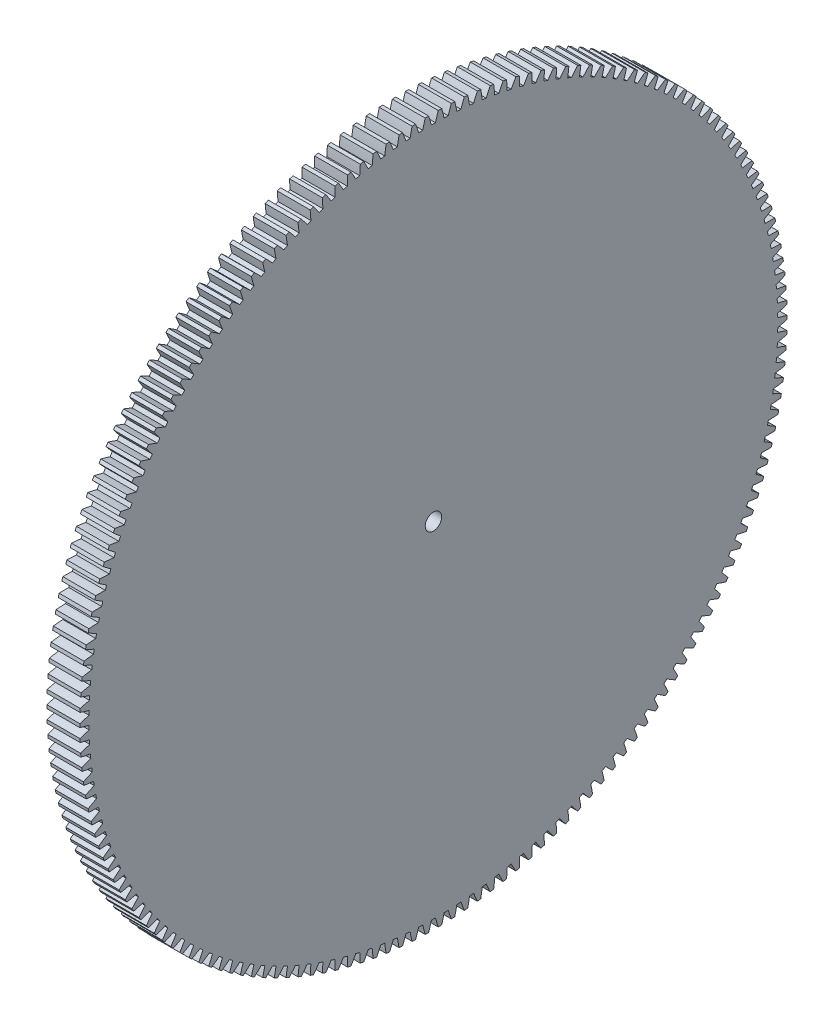
SolidWorks part; units mm, degrees
ref_plane "Plane1" through (0, 0, 0) normal (0, 0, 1) x (1, 0, 0)
ref_plane "Plane2" through (0, 0, 0) normal (0, 1, 0) x (1, 0, 0)
ref_plane "Plane3" through (0, 0, 0) normal (1, 0, 0) x (0, 0, -1)
other "Configuration Table"
sketch "HoldingSke" plane through (0, 0, 0) normal (0, 1, 0) x (1, 0, 0)
  line L0 (0, 0) -> (-1.9696, -0.3473)
  line L1 (-15, 0) -> (100, 0) construction
  line L2 (0, 0) -> (-2.1039, 2.3779)
  line L3 (0, 0) -> (-11.863, 4.5341)
  line L4 (0, 0) -> (-8.5048, 1.4996)
  line L5 (0, 0) -> (-46.8476, -17.4728)
  line L6 (0, 0) -> (-3.3159, -2.2372)
  line L7 (-2.1039, 2.3779) -> (8.6586, 51.2059)
  line L8 (-76.2, 54.61) -> (-75.9, 54.61)
  line L9 (-67.7845, 28.3722) -> (-49.3413, 33.142)
  line L10 (-76.2, 71.12) -> (104.1128, 71.12)
  line L11 (0, 0) -> (-4, 0)
  line L12 (-76.2, 101.6) -> (-76.181, 101.6)
  line L13 (24.9733, 27.94) -> (52.9518, 28.4284)
  line L14 (24.9733, 27.94) -> (24.9743, 27.94)
  line L15 (24.9733, 27.94) -> (100.4006, 29.5858)
  line L16 (-63.627, -0.5) -> (-12.827, -0.5)
  circle A0 centre (0, 0) radius 1
  circle A1 centre (0, 0) radius 37.5
  circle A2 centre (0, 0) radius 37.5
  circle A3 centre (0, 0) radius 1
  dimension "Pitch_radius" = 180.3128
  dimension "Width" = 4
  dimension "Thickness" = 4
sketch "BasProSke" plane through (0, 0, 0) normal (0, 1, 0) x (1, 0, 0)
  line L0 (-10, 0) -> (60, 0) construction
  line L1 (0, 0) -> (0, 43)
  line L2 (0, 0) -> (4, 0)
  line L3 (4, 0) -> (4, 43)
  line L4 (4, 43) -> (0, 43)
  dimension "Thickness" = 4
revolve "Base-Revolve" add sketch "BasProSke" angle 360 about L0
sketch "TooCutSke" plane through (0, 0, 0) normal (1, 0, 0) x (0, 0, -1)
  line L1 (0, 0) -> (0, 107) construction
  line L2 (0, 0) -> (-0.4259, 42.4979) construction
  line L3 (0, 0) -> (-1.5707, 84.9824) construction
  line L4 (-0.4259, 42.4979) -> (-0.7853, 42.4912) construction
  arc A0 (0.251, 41.8732) -> (-0.251, 41.8732) centre (0, 0) ccw
  arc A1 (0.5926, 43.0213) -> (-0.5926, 43.0213) centre (0, 0) ccw
  circle A2 centre (0, 0) radius 42.5 construction
  circle A3 centre (0, 0) radius 41.1463 construction
  arc A4 (-0.251, 41.8732) -> (-0.5926, 43.0213) centre (-16.7058, 37.6023) ccw
  arc A5 (0.5926, 43.0213) -> (0.251, 41.8732) centre (16.7058, 37.6023) ccw
extrude "ToothCut" cut sketch "TooCutSke" along normal through all
fillet "Breaks" [suppressed] radius 0.01 tangent propagation no
fillet "RootFillets" [suppressed] radius 0.126
pattern_circular "TeethCuts" count 170 every 2.118 about axis through (-10, 0, 0) along (1, 0, 0) of "ToothCut", "RootFillets", "Breaks"
sketch "HubNeaOneSke" plane through (0, 0, 0) normal (-1, 0, 0) x (0, 0, 1)
  circle A0 centre (0, 0) radius 37.5
  dimension "Diameter" = 75
extrude "HubNearOne" [suppressed] add sketch "HubNeaOneSke" along normal blind 46.0001
sketch "HubNeaBotSke" plane through (0, 0, 0) normal (-1, 0, 0) x (0, 0, 1)
  circle A0 centre (0, 0) radius 37.5
  dimension "Diameter" = 75
extrude "HubNearBoth" [suppressed] add sketch "HubNeaBotSke" along normal blind 23
ref_plane "FarPln" through (4, 0, 0) normal (1, 0, 0) x (0, 0, -1)
sketch "HubFarSke" plane through (4, 0, 0) normal (1, 0, 0) x (0, 0, -1)
  circle A0 centre (0, 0) radius 37.5
  dimension "Diameter" = 75
extrude "HubFar" [suppressed] add sketch "HubFarSke" along normal blind 23
sketch "BorSke" plane through (0, 0, 0) normal (1, 0, 0) x (0, 0, -1)
  circle A0 centre (0, 0) radius 1
  dimension "Diameter" = 2
extrude "Bore" cut sketch "BorSke" along normal mid plane 100.0001
sketch "KeySke" plane through (0, 0, 0) normal (1, 0, 0) x (0, 0, -1)
  line L0 (-0.4, 0) -> (-0.4, 1.3)
  line L1 (-0.4, 1.3) -> (0.4, 1.3)
  line L2 (0.4, 1.3) -> (0.4, 0)
  line L3 (0, 0) -> (0, 34) construction
  line L4 (-0.4, 0) -> (0.4, 0)
  dimension "Width" = 0.8
extrude "Keyway" [suppressed] cut sketch "KeySke" along normal mid plane 100.0001
pattern_circular "Keyway2" [suppressed] count 2 every 90 about axis through (-10, 0, 0) along (1, 0, 0) reverse direction yes
equation "' \"Module@HoldingSke\" = 6.35"
equation "' \"Num_teeth@HoldingSke\" = 12"
equation "' \"Ap@HoldingSke\" =  20"
equation "' \"Ap@HoldingSke\" = 20"
equation "' \"Width@HoldingSke\" = 0.5 * 25.4"
equation "' \"Hub_dia@HoldingSke\"= 1 * 25.4"
equation "' \"Hub_dia@HoldingSke\" = 1 * 25.4"
equation "' \"Overall_len@HoldingSke\" = 1.0 * 25.4"
equation "' \"Bore@HoldingSke\" = 0.75 * 25.4"
equation "' \"T_dim@HoldingSke\" = 0.1 * 25.4"
equation "' \"Width@KeySke\" = 0.25 * 25.4"
equation "' \"Show_teeth@HoldingSke\" = 13"
equation "' \"Backlash@HoldingSke\" = 0.009 * 25.4"
equation "' \"Addendum_fac@HoldingSke\" = 1.0"
equation "' \"Dedendum_fac@HoldingSke\" = 1.25"
equation "' \"Dedendum_add@HoldingSke\" = 0.00005 * 25.4"
equation "' \"Clearance_fac@HoldingSke\" = 0.25"
equation "\"Pitch@HoldingSke\" = 1 / \"Module@HoldingSke\""
equation "\"Overcut_dia@TooCutSke\" = (\"Num_teeth@HoldingSke\" + 2 * \"Addendum_fac@HoldingSke\") / \"Pitch@HoldingSke\" + 0.002 * 25.4"
equation "\"Pitch_dia@TooCutSke\" = \"Num_teeth@HoldingSke\" / \"Pitch@HoldingSke\""
equation "\"Base_dia@TooCutSke\" = \"Num_teeth@HoldingSke\" / \"Pitch@HoldingSke\" * cos((\"Ap@HoldingSke\"  * 3.14159265 / 180))"
equation "\"Root_dia@TooCutSke\" = (\"Num_teeth@HoldingSke\" + 2) / \"Pitch@HoldingSke\" - 2 * (\"Addendum_fac@HoldingSke\" + \"Dedendum_fac@HoldingSke\") / \"Pitch@HoldingSke\" - \"Dedendum_add@HoldingSke\" * 2"
equation "\"Half_ang@TooCutSke\" = 180 / \"Num_teeth@HoldingSke\""
equation "\"Half_CT@TooCutSke\" = \"Num_teeth@HoldingSke\" / \"Pitch@HoldingSke\" * sin((3.14159265 / 2 / \"Num_teeth@HoldingSke\")) / 2 - 7 * \"Backlash@HoldingSke\" / 4"
equation "\"Flank_rad@TooCutSke\" = \"Num_teeth@HoldingSke\" / \"Pitch@HoldingSke\" / 5"
equation "\"Radius@RootFillets\" = \"Clearance_fac@HoldingSke\" / \"Pitch@HoldingSke\" + \"Dedendum_add@HoldingSke\""
equation "\"Break_rad@Breaks\" = 0.02 / \"Pitch@HoldingSke\""
equation "\"Thickness@HoldingSke\" = \"Width@HoldingSke\""
equation "\"OAL@HoldingSke\" = \"Thickness@HoldingSke\""
equation "\"MHD@HoldingSke\" = (\"Num_teeth@HoldingSke\" + 2) / \"Pitch@HoldingSke\" - 2 * (\"Addendum_fac@HoldingSke\" + \"Dedendum_fac@HoldingSke\")  / \"Pitch@HoldingSke\" - \"Dedendum_add@HoldingSke\" * 2"
equation "\"MBD@HoldingSke\" = (\"Num_teeth@HoldingSke\" + 2) / \"Pitch@HoldingSke\" - 2 * (\"Addendum_fac@HoldingSke\" + \"Dedendum_fac@HoldingSke\")  / \"Pitch@HoldingSke\" - \"Dedendum_add@HoldingSke\" * 2 - 0.002 * 25.4"
equation "\"MHD@HoldingSke\" = ((sgn( \"MHD@HoldingSke\" - \"Hub_dia@HoldingSke\" )-1)*( \"MHD@HoldingSke\" - \"Hub_dia@HoldingSke\" ))/-2+ \"Hub_dia@HoldingSke\""
equation "\"MBD@HoldingSke\" = ((sgn( \"MBD@HoldingSke\" - \"Bore@HoldingSke\" )-1)*( \"MBD@HoldingSke\" - \"Bore@HoldingSke\" ))/-2+ \"Bore@HoldingSke\""
equation "\"OAL@HoldingSke\" = ((sgn( \"OAL@HoldingSke\" - \"Overall_len@HoldingSke\" )+1)*( \"OAL@HoldingSke\" - \"Overall_len@HoldingSke\" ))/2 + \"Overall_len@HoldingSke\" + 0.000002 * 25.4"
equation "\"Num_teeth@TeethCuts\" = int( \"Show_teeth@HoldingSke\" ) + 1"
equation "\"Num_teeth@TeethCuts\" = ((sgn( \"Num_teeth@TeethCuts\" - \"Num_teeth@HoldingSke\" )-1)*( \"Num_teeth@TeethCuts\" - \"Num_teeth@HoldingSke\" ))/-2+ \"Num_teeth@HoldingSke\""
equation "\"Num_teeth@TeethCuts\" = ((sgn( \"Num_teeth@TeethCuts\" - 2.0)+1)*( \"Num_teeth@TeethCuts\" - 2.0))/2 +2.0"
equation "\"Angle@TeethCuts\" = 360.0 / \"Num_teeth@HoldingSke\""
equation "\"Diameter@BasProSke\" = (\"Num_teeth@HoldingSke\" + 2 * \"Addendum_fac@HoldingSke\") / \"Pitch@HoldingSke\""
equation "\"Thickness@BasProSke\"  = \"Thickness@HoldingSke\""
equation "' \"Fillet_rad@BasProSke\" =  \"Thickness@HoldingSke\" * 0.05"
equation "' \"Fillet_rad@BasProSke\" = \"Thickness@HoldingSke\" * 0.05"
equation "\"MHD@HoldingSke\" = ((sgn( \"MHD@HoldingSke\" - \"Root_dia@TooCutSke\" )-1)*( \"MHD@HoldingSke\" - \"Root_dia@TooCutSke\" ))/-2+ \"Root_dia@TooCutSke\""
equation "\"Diameter@HubNeaOneSke\" = \"MHD@HoldingSke\""
equation "\"Length@HubNearOne\" = \"OAL@HoldingSke\" - \"Thickness@BasProSke\""
equation "\"Diameter@HubNeaBotSke\" = \"MHD@HoldingSke\""
equation "\"Length@HubNearBoth\" = ( \"OAL@HoldingSke\" - \"Thickness@BasProSke\" ) / 2.0"
equation "\"Thickness@FarPln\" = \"Thickness@BasProSke\""
equation "\"Diameter@HubFarSke\" = \"MHD@HoldingSke\""
equation "\"Length@HubFar\" = ( \"OAL@HoldingSke\" - \"Thickness@BasProSke\" ) / 2.0"
equation "\"Diameter@BorSke\" = \"MBD@HoldingSke\""
equation "\"D1@Bore\" = \"OAL@HoldingSke\" * 2.0"
equation "\"D1@Keyway\" = \"OAL@HoldingSke\" * 2.0"
equation "\"Offset@KeySke\" = \"T_dim@HoldingSke\" + \"MBD@HoldingSke\" / 2.0"
